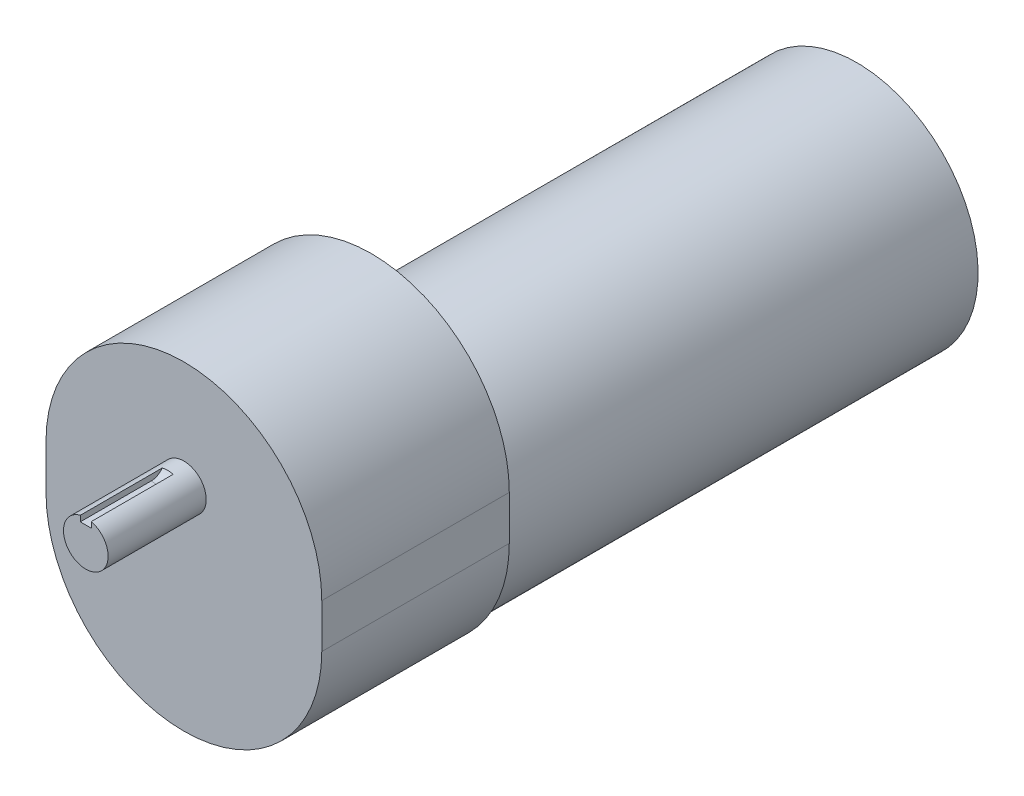
SolidWorks part; units mm, degrees
ref_plane "Front Plane" through (0, 0, 0) normal (0, 0, 1) x (1, 0, 0)
ref_plane "Top Plane" through (0, 0, 0) normal (0, 1, 0) x (1, 0, 0)
ref_plane "Right Plane" through (0, 0, 0) normal (1, 0, 0) x (0, 0, -1)
sketch "Sketch1" plane through (0, 0, 0) normal (0, 0, 1) x (1, 0, 0)
  circle A0 centre (0, 0) radius 12.846
  dimension "D1" = 25.6921
extrude "Boss-Extrude1" add sketch "Sketch1" against normal blind 56.4642
sketch "Sketch2" plane through (0, 0, -56.4642) normal (0, 0, -1) x (-1, 0, 0)
  line L0 (0, -17.0878) -> (0, -42.4878) construction
  line L1 (79.375, -17.0878) -> (79.375, -42.4878)
  line L2 (-79.375, -17.0878) -> (-79.375, -42.4879)
  arc A0 (79.375, -17.0878) -> (-79.375, -17.0878) centre (0, -17.0878) ccw
  arc A1 (-79.375, -42.4879) -> (79.375, -42.4878) centre (0, -42.4878) ccw
  point P3 (0, -29.7878)
  point P8 (0, -121.8628)
  point P9 (0, 62.2872)
  dimension "D1" = 158.75
  dimension "D2" = 184.15
  dimension "D3" = 121.8628
extrude "Boss-Extrude2" add sketch "Sketch2" along normal blind 107.95
sketch "Sketch3" plane through (0, 0, -164.4142) normal (0, 0, -1) x (-1, 0, 0)
  circle A0 centre (0, -52.0129) radius 69.85
  arc A1 (-79.375, -42.4878) -> (79.375, -42.4878) centre (0, -42.4878) ccw construction
  point P5 (0, -121.8628)
  dimension "D1" = 139.7
extrude "Boss-Extrude3" add sketch "Sketch3" along normal blind 279.4
sketch "Sketch4" plane through (0, 0, 0) normal (0, 0, 1) x (1, 0, 0)
  line L0 (-3.1623, 12.4507) -> (-3.1623, 9.1487)
  line L1 (-3.1623, 9.1487) -> (3.1623, 9.1487)
  line L2 (3.1623, 9.1487) -> (3.1623, 12.4507)
  circle A0 centre (0, 0) radius 12.846 construction
  arc A1 (-3.1623, 12.4507) -> (3.1623, 12.4507) centre (0, 0) cw
  point P4 (0, 9.1487)
  dimension "D1" = 6.3246
  dimension "D2" = 3.302
extrude "Cut-Extrude1" cut sketch "Sketch4" against normal blind 47.1297 contours L1 L2 A1 L0
fillet "Fillet1" radius 7.62 1 edges at (0, 9.1487, -47.1297)
